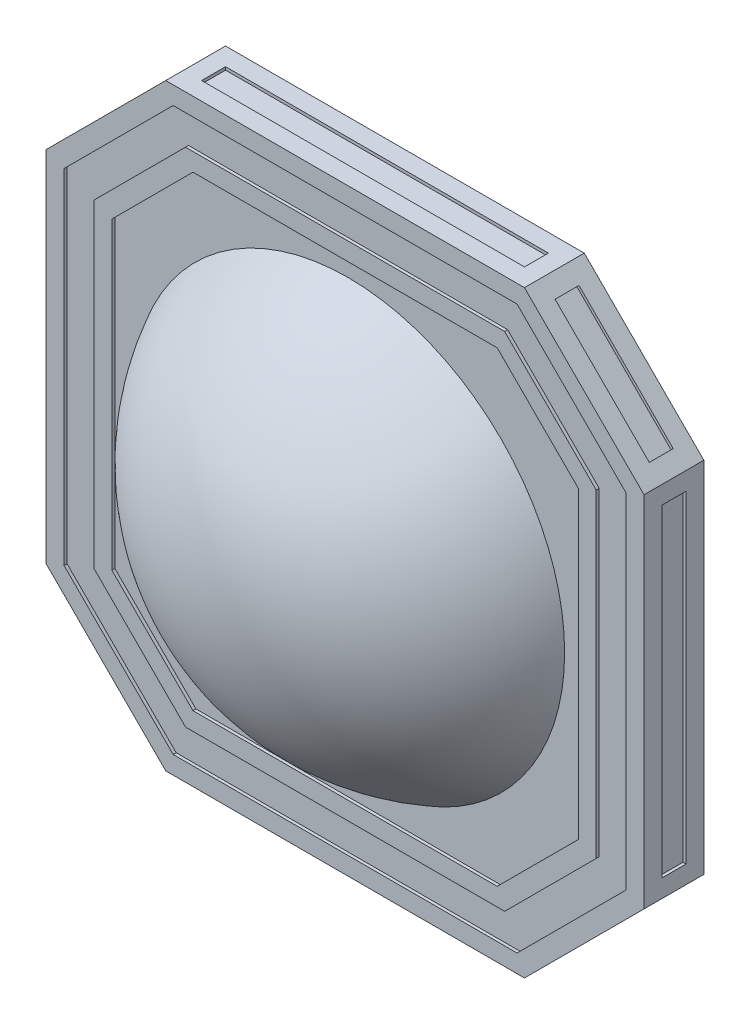
SolidWorks part; units mm, degrees
ref_plane "Front Plane" through (0, 0, 0) normal (0, 0, 1) x (1, 0, 0)
ref_plane "Top Plane" through (0, 0, 0) normal (0, 1, 0) x (1, 0, 0)
ref_plane "Right Plane" through (0, 0, 0) normal (1, 0, 0) x (0, 0, -1)
sketch "Sketch2" plane through (0, 0, 0) normal (0, 0, 1) x (1, 0, 0)
  line L0 (-30, -50) -> (-50, -30)
  line L1 (-50, 50) -> (50, 50)
  line L2 (-50, 50) -> (-50, -50)
  line L3 (-50, -50) -> (50, -50)
  line L4 (50, 50) -> (50, -50)
  line L5 (-50, -50) -> (-30, -50)
  line L6 (-50, -50) -> (-50, -30)
  line L7 (-50, -30) -> (-30, -30)
  line L8 (-30, -50) -> (-30, -30)
  line L9 (0, -60.3584) -> (0, 58.293) construction
  line L10 (64.4154, 0) -> (-60.0437, 0) construction
  line L11 (-30, 50) -> (-50, 30)
  line L12 (30, -50) -> (50, -30)
  line L13 (30, 50) -> (50, 30)
  dimension "D1" = 100
  dimension "D2" = 100
  dimension "D3" = 50
  dimension "D4" = 50
  dimension "D5" = 20
  dimension "D6" = 20
extrude "Boss-Extrude1" add sketch "Sketch2" along normal blind 9.5 contours L13 L1 L11 L2 L7 L8 L3 L12 L4 | L0 L8 L7 region at (0.8148, 0.8148, 0) region at (-36.6667, -36.6667, 0)
sketch "Sketch3" plane through (0, 0, 9.5) normal (0, 0, 1) x (1, 0, 0)
  line L8 (50, 30) -> (30, 50)
  line L9 (30, 50) -> (-30, 50)
  line L10 (-30, 50) -> (-50, 30)
  line L11 (-50, 30) -> (-50, -30)
  line L12 (-50, -30) -> (-30, -50)
  line L13 (-30, -50) -> (30, -50)
  line L14 (30, -50) -> (50, -30)
  line L15 (50, -30) -> (50, 30)
  line L16 (50, 30) -> (30, 50)
  line L17 (30, 50) -> (-30, 50)
  line L18 (-30, 50) -> (-50, 30)
  line L19 (-50, 30) -> (-50, -30)
  line L20 (-50, -30) -> (-30, -50)
  line L21 (-30, -50) -> (30, -50)
  line L22 (30, -50) -> (50, -30)
  line L23 (50, -30) -> (50, 30)
  line L32 (47, 28.7574) -> (28.7574, 47)
  line L33 (28.7574, 47) -> (-28.7574, 47)
  line L34 (-28.7574, 47) -> (-47, 28.7574)
  line L35 (-47, 28.7574) -> (-47, -28.7574)
  line L36 (-47, -28.7574) -> (-28.7574, -47)
  line L37 (-28.7574, -47) -> (28.7574, -47)
  line L38 (28.7574, -47) -> (47, -28.7574)
  line L39 (47, -28.7574) -> (47, 28.7574)
  line L40 (47, 28.7574) -> (28.7574, 47)
  line L41 (28.7574, 47) -> (-28.7574, 47)
  line L42 (-28.7574, 47) -> (-47, 28.7574)
  line L43 (-47, 28.7574) -> (-47, -28.7574)
  line L44 (-47, -28.7574) -> (-28.7574, -47)
  line L45 (-28.7574, -47) -> (28.7574, -47)
  line L46 (28.7574, -47) -> (47, -28.7574)
  line L47 (47, -28.7574) -> (47, 28.7574)
  line L56 (42, 26.6863) -> (26.6863, 42)
  line L57 (26.6863, 42) -> (-26.6863, 42)
  line L58 (-26.6863, 42) -> (-42, 26.6863)
  line L59 (-42, 26.6863) -> (-42, -26.6863)
  line L60 (-42, -26.6863) -> (-26.6863, -42)
  line L61 (-26.6863, -42) -> (26.6863, -42)
  line L62 (26.6863, -42) -> (42, -26.6863)
  line L63 (42, -26.6863) -> (42, 26.6863)
  line L64 (42, 26.6863) -> (26.6863, 42)
  line L65 (26.6863, 42) -> (-26.6863, 42)
  line L66 (-26.6863, 42) -> (-42, 26.6863)
  line L67 (-42, 26.6863) -> (-42, -26.6863)
  line L68 (-42, -26.6863) -> (-26.6863, -42)
  line L69 (-26.6863, -42) -> (26.6863, -42)
  line L70 (26.6863, -42) -> (42, -26.6863)
  line L71 (42, -26.6863) -> (42, 26.6863)
  line L80 (39, 25.4437) -> (25.4437, 39)
  line L81 (25.4437, 39) -> (-25.4437, 39)
  line L82 (-25.4437, 39) -> (-39, 25.4437)
  line L83 (-39, 25.4437) -> (-39, -25.4437)
  line L84 (-39, -25.4437) -> (-25.4437, -39)
  line L85 (-25.4437, -39) -> (25.4437, -39)
  line L86 (25.4437, -39) -> (39, -25.4437)
  line L87 (39, -25.4437) -> (39, 25.4437)
  line L88 (39, 25.4437) -> (25.4437, 39)
  line L89 (25.4437, 39) -> (-25.4437, 39)
  line L90 (-25.4437, 39) -> (-39, 25.4437)
  line L91 (-39, 25.4437) -> (-39, -25.4437)
  line L92 (-39, -25.4437) -> (-25.4437, -39)
  line L93 (-25.4437, -39) -> (25.4437, -39)
  line L94 (25.4437, -39) -> (39, -25.4437)
  line L95 (39, -25.4437) -> (39, 25.4437)
  line M33 (50, 30) -> (30, 50)
  line M34 (30, 50) -> (-30, 50)
  line M35 (-30, 50) -> (-50, 30)
  line M36 (-50, 30) -> (-50, -30)
  line M37 (-50, -30) -> (-30, -50)
  line M38 (-30, -50) -> (30, -50)
  line M39 (30, -50) -> (50, -30)
  line M40 (50, -30) -> (50, 30)
  dimension "D1" = 0
  dimension "D2" = 3
  dimension "D3" = 8
  dimension "D4" = 11
extrude "Boss-Extrude2" add sketch "Sketch3" along normal blind 0.5 contours L47 L46 L45 L44 L43 L42 L41 L40 M40 M33 M34 M35 M36 M37 M38 M39 | L70 L71 L64 L65 L66 L67 L68 L69 L95 L94 L93 L92 L91 L90 L89 L88 region at (48.5858, 0, 9.5) region at (40.8121, 0, 9.5)
shell "Shell1" thickness 3 removed face at (0, 0, 0)
sketch "Sketch5" plane through (0, 0, 6.5) normal (0, 0, -1) x (-1, 0, 0)
  line L8 (-28.7574, -47) -> (28.7574, -47)
  line L9 (28.7574, -47) -> (47, -28.7574)
  line L10 (47, -28.7574) -> (47, 28.7574)
  line L11 (47, 28.7574) -> (28.7574, 47)
  line L12 (28.7574, 47) -> (-28.7574, 47)
  line L13 (-28.7574, 47) -> (-47, 28.7574)
  line L14 (-47, 28.7574) -> (-47, -28.7574)
  line L15 (-47, -28.7574) -> (-28.7574, -47)
  line L16 (-28.7574, -47) -> (28.7574, -47)
  line L17 (28.7574, -47) -> (47, -28.7574)
  line L18 (47, -28.7574) -> (47, 28.7574)
  line L19 (47, 28.7574) -> (28.7574, 47)
  line L20 (28.7574, 47) -> (-28.7574, 47)
  line L21 (-28.7574, 47) -> (-47, 28.7574)
  line L22 (-47, 28.7574) -> (-47, -28.7574)
  line L23 (-47, -28.7574) -> (-28.7574, -47)
  circle A0 centre (0, 0) radius 40
  dimension "D2" = 80
  dimension "D1" = 0
extrude "Boss-Extrude3" add sketch "Sketch5" along normal blind 3
extrude "Boss-Extrude4" add sketch "Sketch5<4>" along normal blind 1 contours A0
sketch "Sketch5<4>" plane through (0, 0, 6.5) normal (0, 0, -1) x (-1, 0, 0) same geometry as "Sketch5"
ref_plane "Plane2" through (0, 0, 0) normal (1, 0, 0) x (0, 0, -1)
sketch "Sketch7" plane through (0, 0, 0) normal (1, 0, 0) x (0, 0, -1)
  line L0 (-5.5, -40) -> (-5.5, 40) construction
  line L1 (-5.5, -40) -> (-5.5, 40)
  line L2 (-5.5, 40) -> (-5.5, 38)
  line L3 (-5.5, -40) -> (-5.5, -38)
  line L4 (-35.633, 0) -> (55.8216, 0) construction
  circle A0 centre (9.0291, 0) radius 40.6829
  dimension "D1" = 2
  dimension "D2" = 2
revolve "Revolve1" add sketch "Sketch7" angle 360 about L4 region at (0, -15.1493, 16.3169)
sketch "Sketch8" plane through (0, 0, 0) normal (1, 0, 0) x (0, 0, -1)
  line L1 (-2.5, -40) -> (-2.5, 40)
  line L2 (-2.5, 40) -> (-2.5, 38)
  line L3 (-2.5, -40) -> (-2.5, -38)
  line L4 (-35.633, 0) -> (55.8216, 0) construction
  circle A0 centre (12.0291, 0) radius 40.6829
  circle A1 centre (12.0291, 0) radius 40.6829
  dimension "D1" = 2
  dimension "D2" = 2
  dimension "D3" = 47.6621
shell "Shell4" thickness 1 removed face at (-40, 0, 5.5)
sketch "Sketch11" plane through (0, 0, 0) normal (1, 0, 0) x (0, 0, -1)
  line L0 (-8.5, -35.6014) -> (-8.5, 35.6014) construction
  line L1 (-5.5, 40) -> (-5.5, -40) construction
  line L2 (-8.5, -35.6014) -> (-8.5, 35.6014)
  line L3 (-5.5, 40) -> (-5.5, -40)
  line L4 (-5.5, 0) -> (-8.5, 0)
  line L5 (-8.5, -35.6014) -> (-5.5, -40)
  line L6 (-5.5, -40) -> (-5.5, -41)
  line L8 (-8.5, -35.6014) -> (-8.5, -36.6014)
  line L9 (-5.5, -41) -> (-6.182, -40)
  line L10 (-6.182, -40) -> (-8.5, -40)
  line L11 (-8.5, -26.2721) -> (-8.5, -41) construction
  line L12 (-8.5, -40) -> (-8.5, -36.6014)
  dimension "D1" = 1
  dimension "D2" = 1
revolve "Revolve2" add sketch "Sketch11" angle 360 about L4 region at (0, -38.6222, 7.4129)
sketch "Sketch12" plane through (0, 0, 0) normal (1, 0, 0) x (0, 0, -1)
  line L0 (-9.2224, -49.2309) -> (-0.7887, -49.2309)
  line L1 (-0.7887, -49.2309) -> (-0.7887, -47.7456)
  line L2 (-0.7887, -47.7456) -> (-4.1993, -47.7456)
  line L3 (-4.1993, -47.7456) -> (-4.1993, -40.7028)
  line L4 (-4.1993, -40.7028) -> (-5.4483, -40.7028)
  line L5 (-5.4483, -40.7028) -> (-8.6846, -35.9629)
  line L6 (-8.6846, -35.9629) -> (-8.6846, -39.7214)
  line L7 (-8.6846, -39.7214) -> (-9.2224, -39.7214)
  line L8 (-9.2224, -39.7214) -> (-9.2224, -41.4678)
  line L9 (-9.2224, -41.4678) -> (-8.6846, -41.4678)
  line L10 (-8.6846, -41.4678) -> (-8.6846, -47.7456)
  line L11 (-8.6846, -47.7456) -> (-9.2224, -47.7456)
  line L12 (-9.2224, -47.7456) -> (-9.2224, -49.2309)
  line L13 (6.133, 0) -> (-13.9293, 0) construction
sketch "Sketch13" plane through (0, 0, 0) normal (0, 0, -1) x (-1, 0, 0)
  line L8 (-30, 50) -> (-50, 30)
  line L9 (-50, 30) -> (-50, -30)
  line L10 (-50, -30) -> (-30, -50)
  line L11 (-30, -50) -> (30, -50)
  line L12 (30, -50) -> (50, -30)
  line L13 (50, -30) -> (50, 30)
  line L14 (50, 30) -> (30, 50)
  line L15 (30, 50) -> (-30, 50)
  line L16 (-30, 50) -> (-50, 30)
  line L17 (-50, 30) -> (-50, -30)
  line L18 (-50, -30) -> (-30, -50)
  line L19 (-30, -50) -> (30, -50)
  line L20 (30, -50) -> (50, -30)
  line L21 (50, -30) -> (50, 30)
  line L22 (50, 30) -> (30, 50)
  line L23 (30, 50) -> (-30, 50)
  line L24 (-28.7574, 47) -> (-47, 28.7574)
  line L25 (28.7574, 47) -> (-28.7574, 47)
  line L26 (47, 28.7574) -> (28.7574, 47)
  line L27 (47, -28.7574) -> (47, 28.7574)
  line L28 (28.7574, -47) -> (47, -28.7574)
  line L29 (-28.7574, -47) -> (28.7574, -47)
  line L30 (-47, -28.7574) -> (-28.7574, -47)
  line L31 (-47, 28.7574) -> (-47, -28.7574)
  line L32 (-28.7574, 47) -> (-47, 28.7574)
  line L33 (28.7574, 47) -> (-28.7574, 47)
  line L34 (47, 28.7574) -> (28.7574, 47)
  line L35 (47, -28.7574) -> (47, 28.7574)
  line L36 (28.7574, -47) -> (47, -28.7574)
  line L37 (-28.7574, -47) -> (28.7574, -47)
  line L38 (-47, -28.7574) -> (-28.7574, -47)
  line L39 (-47, 28.7574) -> (-47, -28.7574)
  dimension "D1" = 0
  dimension "D2" = 0
extrude "Boss-Extrude5" add sketch "Sketch13" against normal up to surface (10 mm away) up to face at (0, 0, 10)
sketch "Sketch15" plane through (0, 0, 3.5) normal (0, 0, -1) x (-1, 0, 0)
  line L8 (-47, -28.7574) -> (-28.7574, -47)
  line L9 (-28.7574, -47) -> (28.7574, -47)
  line L10 (28.7574, -47) -> (47, -28.7574)
  line L11 (47, -28.7574) -> (47, 28.7574)
  line L12 (47, 28.7574) -> (28.7574, 47)
  line L13 (28.7574, 47) -> (-28.7574, 47)
  line L14 (-28.7574, 47) -> (-47, 28.7574)
  line L15 (-47, 28.7574) -> (-47, -28.7574)
  line L16 (-47, -28.7574) -> (-28.7574, -47)
  line L17 (-28.7574, -47) -> (28.7574, -47)
  line L18 (28.7574, -47) -> (47, -28.7574)
  line L19 (47, -28.7574) -> (47, 28.7574)
  line L20 (47, 28.7574) -> (28.7574, 47)
  line L21 (28.7574, 47) -> (-28.7574, 47)
  line L22 (-28.7574, 47) -> (-47, 28.7574)
  line L23 (-47, 28.7574) -> (-47, -28.7574)
  circle A0 centre (0, 0) radius 40 construction
  circle A1 centre (0, 0) radius 40
  dimension "D1" = 0
extrude "Boss-Extrude6" add sketch "Sketch15" against normal up to surface (6 mm away) up to face at (0, 0, 9.5)
sketch "Sketch16" plane through (-40, 40, 0) normal (-0.7071, 0.7071, 0) x (0, 0, 1)
  line L4 (0, 14.1421) -> (0, -14.1421)
  line L5 (0, -14.1421) -> (10, -14.1421)
  line L6 (10, -14.1421) -> (10, 14.1421)
  line L7 (10, 14.1421) -> (0, 14.1421)
  line L8 (0, 14.1421) -> (0, -14.1421)
  line L9 (0, -14.1421) -> (10, -14.1421)
  line L10 (10, -14.1421) -> (10, 14.1421)
  line L11 (10, 14.1421) -> (0, 14.1421)
  line L16 (3, 11.1421) -> (3, -11.1421)
  line L17 (3, -11.1421) -> (7, -11.1421)
  line L18 (7, -11.1421) -> (7, 11.1421)
  line L19 (7, 11.1421) -> (3, 11.1421)
  line L20 (3, 11.1421) -> (3, -11.1421)
  line L21 (3, -11.1421) -> (7, -11.1421)
  line L22 (7, -11.1421) -> (7, 11.1421)
  line L23 (7, 11.1421) -> (3, 11.1421)
  dimension "D1" = 0
  dimension "D2" = 3
extrude "Cut-Extrude1" cut sketch "Sketch16" against normal blind 0.5 contours L22 L23 L20 L21
sketch "Sketch17" plane through (-40, -40, 0) normal (-0.7071, -0.7071, 0) x (0, 0, 1)
  line L4 (0, 14.1421) -> (0, -14.1421)
  line L5 (0, -14.1421) -> (10, -14.1421)
  line L6 (10, -14.1421) -> (10, 14.1421)
  line L7 (10, 14.1421) -> (0, 14.1421)
  line L8 (0, 14.1421) -> (0, -14.1421)
  line L9 (0, -14.1421) -> (10, -14.1421)
  line L10 (10, -14.1421) -> (10, 14.1421)
  line L11 (10, 14.1421) -> (0, 14.1421)
  line L13 (3, 11.1421) -> (0, 11.1421)
  line L14 (3, 11.1421) -> (3, -11.1421)
  line L15 (3, -11.1421) -> (0, -11.1421)
  line L16 (3, 11.1421) -> (3, -11.1421)
  line L17 (3, -11.1421) -> (7, -11.1421)
  line L18 (7, -11.1421) -> (7, 11.1421)
  line L19 (7, 11.1421) -> (3, 11.1421)
  line L20 (3, 11.1421) -> (3, -11.1421)
  line L21 (3, -11.1421) -> (7, -11.1421)
  line L22 (7, -11.1421) -> (7, 11.1421)
  line L23 (7, 11.1421) -> (3, 11.1421)
  line L24 (0, 11.1421) -> (0, -11.1421)
  dimension "D1" = 0
  dimension "D2" = 3
extrude "Cut-Extrude3" cut sketch "Sketch17" against normal blind 0.5 contours L22 L23 L14 L21 region at (-40, -40, 5)
sketch "Sketch18" plane through (-50, 0, 0) normal (-1, 0, 0) x (0, 0, 1)
  line L4 (0, 30) -> (0, -30)
  line L5 (0, -30) -> (10, -30)
  line L6 (10, -30) -> (10, 30)
  line L7 (10, 30) -> (0, 30)
  line L8 (0, 30) -> (0, -30)
  line L9 (0, -30) -> (10, -30)
  line L10 (10, -30) -> (10, 30)
  line L11 (10, 30) -> (0, 30)
  line L16 (3, 27) -> (3, -27)
  line L17 (3, -27) -> (7, -27)
  line L18 (7, -27) -> (7, 27)
  line L19 (7, 27) -> (3, 27)
  line L20 (3, 27) -> (3, -27)
  line L21 (3, -27) -> (7, -27)
  line L22 (7, -27) -> (7, 27)
  line L23 (7, 27) -> (3, 27)
  dimension "D1" = 0
  dimension "D2" = 3
extrude "Cut-Extrude4" cut sketch "Sketch18" against normal blind 0.5 contours L20 L21 L22 L23
mirror "Mirror1" about plane through (0, 0, 0) normal (1, 0, 0) of "Cut-Extrude4", "Cut-Extrude3", "Cut-Extrude1"
sketch "Sketch20" plane through (0, 50, 0) normal (0, 1, 0) x (1, 0, 0)
  line L4 (30, 0) -> (-30, 0)
  line L5 (-30, 0) -> (-30, -10)
  line L6 (-30, -10) -> (30, -10)
  line L7 (30, -10) -> (30, 0)
  line L8 (30, 0) -> (-30, 0)
  line L9 (-30, 0) -> (-30, -10)
  line L10 (-30, -10) -> (30, -10)
  line L11 (30, -10) -> (30, 0)
  line L16 (27, -3) -> (-27, -3)
  line L17 (-27, -3) -> (-27, -7)
  line L18 (-27, -7) -> (27, -7)
  line L19 (27, -7) -> (27, -3)
  line L20 (27, -3) -> (-27, -3)
  line L21 (-27, -3) -> (-27, -7)
  line L22 (-27, -7) -> (27, -7)
  line L23 (27, -7) -> (27, -3)
  dimension "D1" = 0
  dimension "D2" = 3
extrude "Cut-Extrude5" cut sketch "Sketch20" against normal blind 0.5 contours L20 L21 L22 L23
ref_plane "Plane3" through (-30, 0, 0) normal (1, 0, 0) x (0, 0, -1)
sketch "Sketch21" plane through (-30, 0, 0) normal (1, 0, 0) x (0, 0, -1)
  line L0 (-10, -50) -> (0, -50) construction
  circle A0 centre (1.5, -47) radius 1.65
  circle A1 centre (1.5, -47) radius 2.86
  circle A2 centre (1.5, -47) radius 3.5
  point P3 (0, -50)
  dimension "D1" = 3.3
  dimension "D2" = 5.72
  dimension "D4" = 7
  dimension "D3" = 1.5
  dimension "D5" = 3
extrude "Cut-Extrude6" cut sketch "Sketch21" along normal blind 2 and the other way blind 10 contours A2 A1 | A1 A0 | A0 region at (-30, -47, -1.5) region at (-30, -47, 1.2791) region at (-30, -47, 1.901)
extrude "Boss-Extrude7" add sketch "Sketch21<5>" along normal blind 17.5 from offset 2 contours A1 A0 region at (-30, -47, 1.2791)
sketch "Sketch21<5>" plane through (-30, 0, 0) normal (1, 0, 0) x (0, 0, -1) same geometry as "Sketch21"
extrude "Cut-Extrude7" cut sketch "Sketch21<6>" along normal blind 20 contours A0 region at (-30, -47, -1.5)
sketch "Sketch21<6>" plane through (-30, 0, 0) normal (1, 0, 0) x (0, 0, -1) same geometry as "Sketch21"
sketch "Sketch22" plane through (-10.5, 0, 0) normal (1, 0, 0) x (0, 0, -1)
  circle A0 centre (1.5, -47) radius 3.5
  dimension "D1" = 7
extrude "Cut-Extrude8" cut sketch "Sketch22" along normal blind 2.5
sketch "Sketch23" plane through (-30, 0, 0) normal (1, 0, 0) x (0, 0, -1)
  line L1 (-2, -47) -> (1.5, -47)
  line L2 (-2, -47) -> (-2, -56.2128)
  line L3 (-2, -56.2128) -> (1.5, -56.2128)
  line L4 (1.5, -47) -> (1.5, -56.2128)
  circle A0 centre (1.5, -47) radius 3.5
  dimension "D1" = 7
extrude "Cut-Extrude10" cut sketch "Sketch23" against normal blind 20 and the other way blind 2 contours A0 L2 L3 L4 | L1 A0 L4 region at (-30, -52.9336, 0.3625) region at (-30, -48.4854, -0.0146)
mirror "Mirror2" about plane through (0, 0, 0) normal (1, 0, 0) of "Cut-Extrude10", "Cut-Extrude6", "Boss-Extrude7", "Cut-Extrude7", "Cut-Extrude8"
extrude "Cut-Extrude9" cut sketch "Sketch22<2>" along normal blind 20
sketch "Sketch22<2>" plane through (-10.5, 0, 0) normal (1, 0, 0) x (0, 0, -1) same geometry as "Sketch22"
